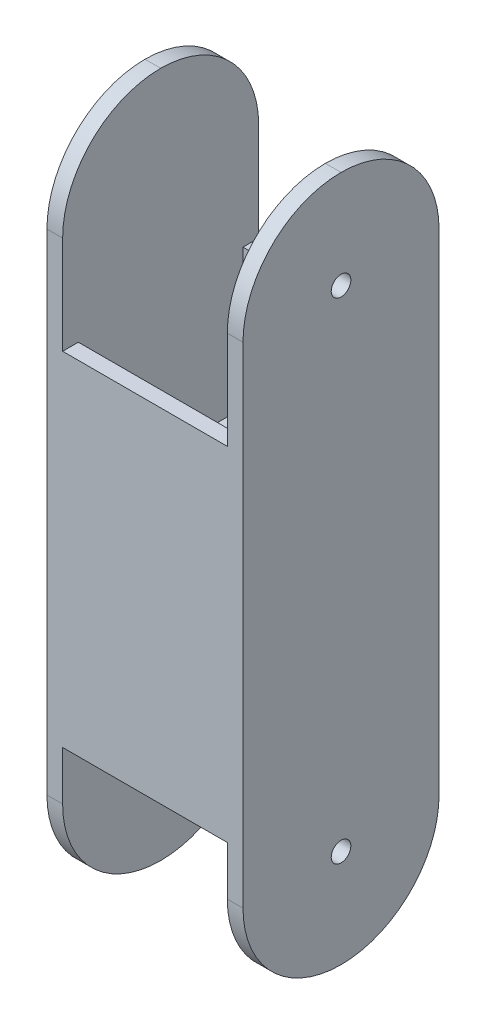
SolidWorks part; units mm, degrees
ref_plane "Front Plane" through (0, 0, 0) normal (0, 0, 1) x (1, 0, 0)
ref_plane "Top Plane" through (0, 0, 0) normal (0, 1, 0) x (1, 0, 0)
ref_plane "Right Plane" through (0, 0, 0) normal (1, 0, 0) x (0, 0, -1)
sketch "Sketch1" plane through (0, 0, 0) normal (0, 0, 1) x (1, 0, 0)
  line L0 (8, -8) -> (8, -171)
  line L1 (0, 0) -> (8, 0)
  line L2 (0, 0) -> (0, -350)
  line L3 (0, -350) -> (8, -350)
  line L4 (100, 0) -> (100, -350)
  line L5 (92, -8) -> (92, -171)
  line L6 (92, 0) -> (100, 0)
  line L7 (92, -350) -> (100, -350)
  line L8 (92, -179) -> (92, -292)
  line L9 (0, 0) -> (8, 0)
  line L10 (0, 0) -> (0, -8)
  line L12 (100, 0) -> (100, -8)
  line L13 (0, -350) -> (8, -350)
  line L14 (0, -350) -> (0, -292)
  line L16 (100, -350) -> (100, -292)
  line L17 (8, -171) -> (92, -171)
  line L18 (0, -146) -> (0, -154)
  line L19 (8, -179) -> (92, -179)
  line L20 (100, -146) -> (100, -154)
  line L21 (8, -179) -> (8, -292)
  line L22 (92, 0) -> (92, -8)
  line L23 (8, 0) -> (8, -8)
  line L24 (92, 0) -> (100, 0)
  line L25 (92, -350) -> (100, -350)
  line L26 (92, -292) -> (92, -350)
  line L27 (8, -292) -> (8, -350)
  dimension "D1" = 171
  dimension "D2" = 100
  dimension "D3" = 8
  dimension "D4" = 8
  dimension "D5" = 171
  dimension "D7" = 8
extrude "Boss-Extrude1" add sketch "Sketch1" along normal blind 100 contours L3 L13 L7 L4 L6 L9 L1 L2 L21 L19 L8 L17 L0 L5 region at (50, -175, 0)
fillet "Fillet1" radius 50 8 edges at (4, 0, 100) (4, 0, 0) (96, -350, 0) (96, -350, 100) (4, -350, 100) (4, -350, 0) (96, 0, 100) (96, 0, 0)
sketch "Sketch2" plane through (100, 0, 0) normal (1, 0, 0) x (0, 0, -1)
  circle A0 centre (-50, -300) radius 5
  circle A1 centre (-50, -50) radius 5
extrude "Cut-Extrude1" cut sketch "Sketch2" against normal blind 10
sketch "Sketch3" plane through (92, 0, 0) normal (-1, 0, 0) x (0, 0, 1)
  circle A0 centre (50, -300) radius 5
  circle A1 centre (50, -300) radius 20
extrude "Boss-Extrude2" add sketch "Sketch3" along normal blind 7.5
sketch "Sketch4" plane through (84.5, 0, 0) normal (-1, 0, 0) x (0, 0, 1)
  circle A0 centre (50, -300) radius 5
  circle A1 centre (50, -300) radius 10
extrude "Boss-Extrude3" add sketch "Sketch4" along normal blind 7.5
sketch "Sketch5" plane through (0, 0, 100) normal (0, 0, 1) x (1, 0, 0)
  line L12 (0, -50) -> (0, -300) construction
  line L13 (0, -100) -> (100, -100)
  line L14 (0, -100) -> (0, -275)
  line L15 (0, -275) -> (100, -275)
  line L16 (100, -100) -> (100, -275)
  line L17 (100, -50) -> (100, -300) construction
  line L18 (8, -50) -> (0, -50) construction
  dimension "D1" = 175
  dimension "D2" = 50
extrude "Boss-Extrude4" add sketch "Sketch5" against normal blind 8
sketch "Sketch6" plane through (0, 0, 0) normal (0, 0, -1) x (-1, 0, 0)
  line L9 (-92, -100) -> (-8, -100)
  line L10 (-92, -100) -> (-92, -275)
  line L11 (-92, -275) -> (-8, -275)
  line L12 (-8, -100) -> (-8, -275)
extrude "Boss-Extrude6" add sketch "Sketch6" against normal blind 8
